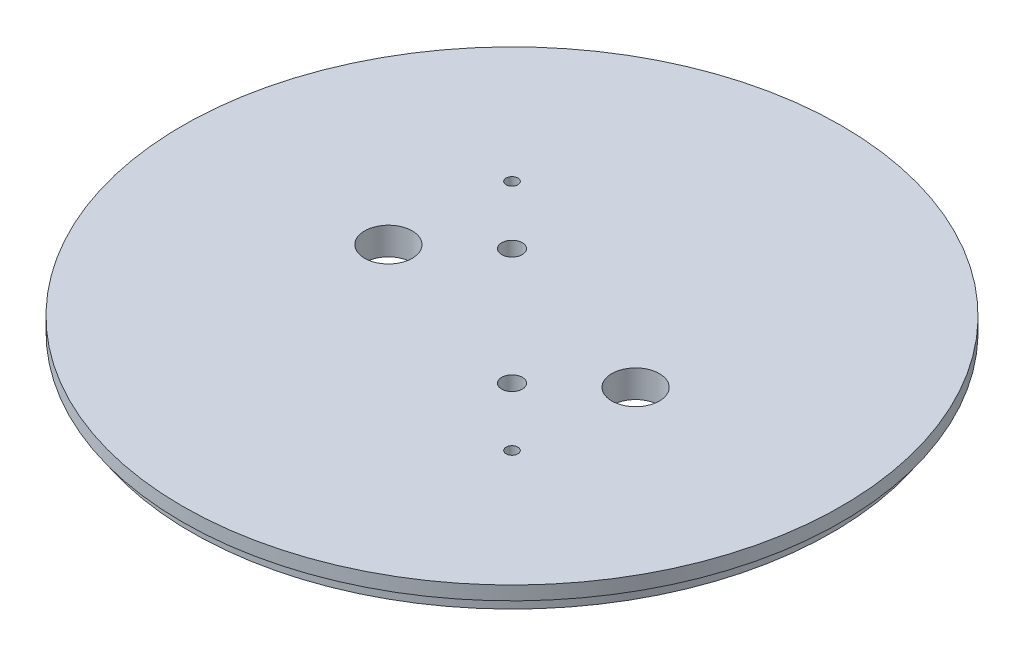
SolidWorks part; units mm, degrees
material "6061-T6 (SS)"
ref_plane "Front Plane" through (0, 0, 0) normal (0, 0, 1) x (1, 0, 0)
ref_plane "Top Plane" through (0, 0, 0) normal (0, 1, 0) x (1, 0, 0)
ref_plane "Right Plane" through (0, 0, 0) normal (1, 0, 0) x (0, 0, -1)
sketch "Sketch1" plane through (0, 0, 0) normal (0, 1, 0) x (1, 0, 0)
  line L0 (0, -76.2) -> (0, 76.2) construction
  line L1 (-76.2, 0) -> (76.2, 0) construction
  line L2 (-26.9408, 26.9408) -> (0, 0) construction
  line L3 (0, 56.7387) -> (0, 29.6936) construction
  line L4 (3.6407, 56.7387) -> (3.6407, 29.6936) construction
  line L5 (-3.6407, 56.7387) -> (-3.6407, 29.6936) construction
  line L6 (0, -56.7387) -> (0, -29.6936) construction
  line L7 (3.6407, -56.7387) -> (3.6407, -29.6936) construction
  line L8 (-3.6407, -56.7387) -> (-3.6407, -29.6936) construction
  line L9 (-53.8815, -53.8815) -> (54.3236, 54.3236) construction
  circle A0 centre (0, 0) radius 76.2
  circle A1 centre (0, 0) radius 3.175 construction
  circle A2 centre (28.575, 0) radius 5.5
  circle A3 centre (-28.575, 0) radius 5.5
  circle A4 centre (-26.9408, 26.9408) radius 1.3589
  arc A6 (3.6407, 56.7387) -> (-3.6407, 56.7387) centre (0, 56.7387) ccw construction
  arc A7 (-3.6407, 29.6936) -> (3.6407, 29.6936) centre (0, 29.6936) ccw construction
  arc A8 (3.6407, -56.7387) -> (-3.6407, -56.7387) centre (0, -56.7387) cw construction
  arc A9 (-3.6407, -29.6936) -> (3.6407, -29.6936) centre (0, -29.6936) cw construction
  circle A10 centre (26.9408, -26.9408) radius 1.3589
  circle A11 centre (-13.4704, 13.4704) radius 2.3813
  circle A12 centre (13.4704, -13.4704) radius 2.3813
  point P16 (0, 43.2162)
  point P19 (0, 0)
  point P26 (0, -43.2162)
  dimension "D1" = 152.4
  dimension "D2" = 6.35
  dimension "D3" = 11
  dimension "D5" = 2.7178
  dimension "D8" = 4.7625
  dimension "D6" = 38.1
  dimension "D7" = 45
  dimension "D4" = 45
  dimension "D9" = 28.575
extrude "Boss-Extrude1" add sketch "Sketch1" along normal blind 6.35
sketch "Sketch2" plane through (0, 0, 0) normal (0, -1, 0) x (1, 0, 0)
  circle A0 centre (0, 0) radius 76.2
  circle A1 centre (0, 0) radius 74.041
  dimension "D1" = 152.4
  dimension "D2" = 148.082
extrude "Cut-Extrude1" cut sketch "Sketch2" against normal blind 3.175
sketch "Sketch3" plane through (0, 6.35, 0) normal (0, 1, 0) x (1, 0, 0)
  line L0 (0, 76.2) -> (0, -76.2) construction
  line L1 (-76.2, 0) -> (76.2, 0) construction
  line L2 (0, 34.798) -> (0, 13.97) construction
  line L3 (3.2385, 34.798) -> (3.2385, 13.97)
  line L4 (-3.2385, 34.798) -> (-3.2385, 13.97)
  line L5 (0, -34.798) -> (0, -13.97) construction
  line L6 (3.2385, -34.798) -> (3.2385, -13.97)
  line L7 (-3.2385, -34.798) -> (-3.2385, -13.97)
  circle A0 centre (0, 0) radius 76.2 construction
  arc A1 (3.2385, 34.798) -> (-3.2385, 34.798) centre (0, 34.798) ccw
  arc A2 (-3.2385, 13.97) -> (3.2385, 13.97) centre (0, 13.97) ccw
  arc A3 (3.2385, -34.798) -> (-3.2385, -34.798) centre (0, -34.798) cw
  arc A4 (-3.2385, -13.97) -> (3.2385, -13.97) centre (0, -13.97) cw
  point P7 (0, 13.97)
  point P8 (0, 34.798)
  point P12 (0, 24.384)
  point P20 (0, -24.384)
  point P25 (0, -34.798)
  point P26 (0, -13.97)
  dimension "D1" = 13.97
  dimension "D2" = 20.828
  dimension "D3" = 6.477
extrude "Cut-Extrude2" cut sketch "Sketch3" against normal blind 3.556 from offset 5.969 offset against normal yes
equation "\"leadDist\"=1.5"
equation "\"Lead_Screw_Dist\" = 2.25in"
equation "\"D9@Sketch1\"=\"Lead_Screw_Dist\"/2"
equation "\"Lead_Screw_Diam\" = 11mm"
equation "\"D3@Sketch1\"=\"Lead_Screw_Diam\""
